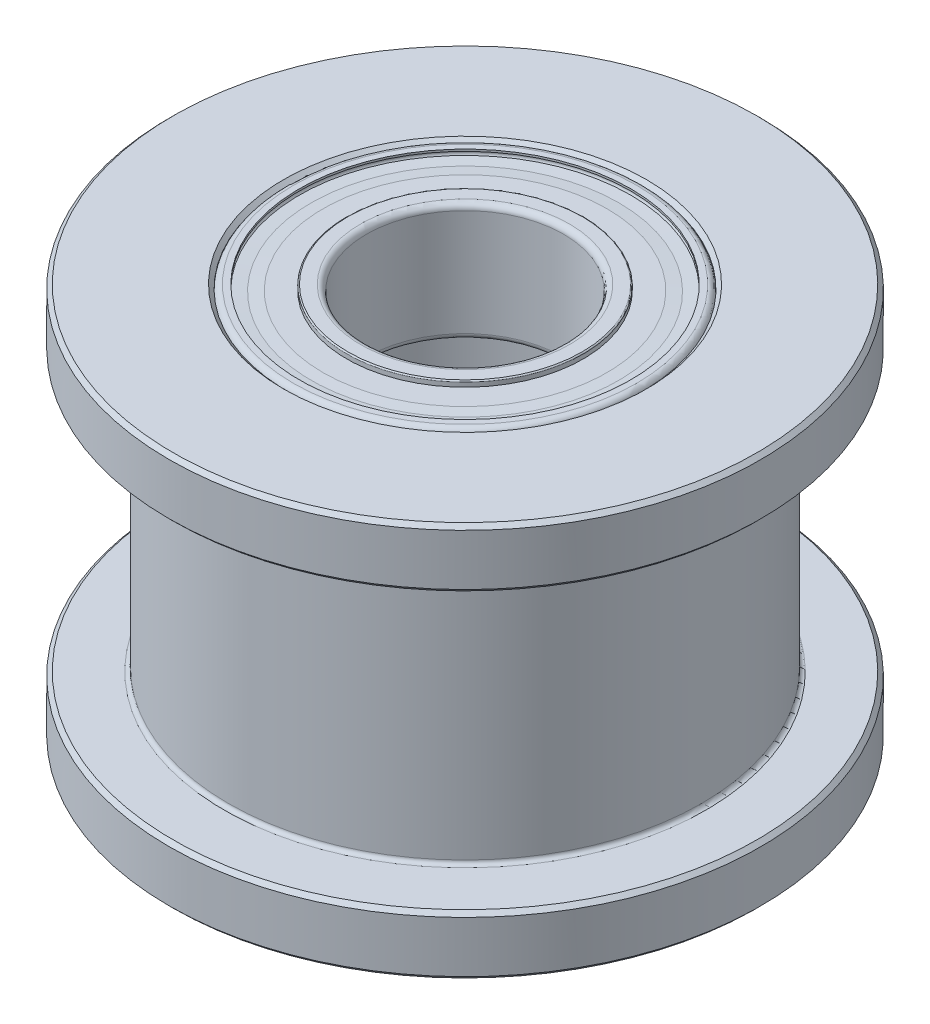
SolidWorks part; units mm, degrees
material "6061-T6 (SS)"
ref_plane "Přední rovina" through (0, 0, 0) normal (0, 0, 1) x (1, 0, 0)
ref_plane "Horní rovina" through (0, 0, 0) normal (0, 1, 0) x (1, 0, 0)
ref_plane "Pravá rovina" through (0, 0, 0) normal (1, 0, 0) x (0, 0, -1)
sketch "Skica1" plane through (0, 0, 0) normal (0, 0, 1) x (1, 0, 0)
  line L0 (4.5, 10) -> (7.5, 10)
  line L1 (7.5, 10) -> (7.5, 8.5)
  line L2 (7.5, 8.5) -> (6, 8.5)
  line L3 (6, 8.5) -> (6, 1.5)
  line L4 (6, 1.5) -> (7.5, 1.5)
  line L5 (7.5, 1.5) -> (7.5, 0)
  line L6 (7.5, 0) -> (4.5, 0)
  line L8 (4.5, 10) -> (4.5, 7)
  line L9 (4.5, 7) -> (3.5, 7)
  line L10 (3.5, 7) -> (3.5, 3)
  line L11 (3.5, 3) -> (4.5, 3)
  line L12 (4.5, 3) -> (4.5, 0)
  line L13 (0, 0) -> (0, -4.1646) construction
  dimension "D1" = 1.5
  dimension "D2" = 7
  dimension "D3" = 4.5
  dimension "D4" = 3.5
  dimension "D5" = 6
  dimension "D6" = 3
  dimension "D7" = 7.5
revolve "Rotovat1" add sketch "Skica1" angle 360 about L13
chamfer "Zkosení1" distance 0.1 angle 45 8 edges at (0, 3, 3.5) (0, 0, 4.5) (0, 7, 3.5) (0, 0, 7.5) (0, 1.5, 7.5) (0, 8.5, 7.5) (0, 10, 7.5) (0, 10, 4.5)
fillet "Zaoblit1" radius 0.1 4 edges at (0, 3, 4.5) (0, 1.5, 6) (0, 8.5, 6) (0, 7, 4.5)
sketch "Skica4" plane through (0, 0, 0) normal (0, 0, 1) x (1, 0, 0)
  line L0 (4.5, 9.85) -> (4.5, 7.15)
  line L1 (4.35, 7) -> (4.2, 7)
  line L2 (4.2, 7) -> (4.2, 7.05)
  line L3 (3.85, 7.2828) -> (4.2132, 7.229)
  line L4 (3.85, 7.2828) -> (3.85, 8.0528)
  line L5 (3.85, 8.9472) -> (3.85, 9.7172)
  line L6 (3.85, 9.7172) -> (4.2132, 9.771)
  line L7 (4.35, 10) -> (4.2, 10)
  line L8 (4.2, 10) -> (4.2, 9.95)
  line L9 (0, 0) -> (0, 18.4294) construction
  line L10 (4.4, 7) -> (-4.4, 7) construction
  arc A0 (4.35, 10) -> (4.5, 9.85) centre (4.35, 9.85) cw
  arc A1 (4.35, 7) -> (4.5, 7.15) centre (4.35, 7.15) ccw
  arc A2 (4.2, 9.95) -> (4.2132, 9.771) centre (4.2, 9.86) cw
  arc A3 (3.85, 8.9472) -> (3.85, 8.0528) centre (3.45, 8.5) cw
  arc A4 (4.2, 7.05) -> (4.2132, 7.229) centre (4.2, 7.14) ccw
  point P26 (4.5, 8.5)
  point P29 (4.275, 7)
  dimension "D3" = 0.09
  dimension "D6" = 0.15
  dimension "D7" = 0.6
  dimension "D1" = 4.5
  dimension "D2" = 3.85
  dimension "D4" = 0.05
  dimension "D5" = 0.15
  dimension "D8" = 0.77
  dimension "D9" = 3
  dimension "D10" = 1.05
revolve "Rotovat2" add sketch "Skica4" angle 360 about L9
sketch "Skica5" plane through (0, 0, 0) normal (0, 0, 1) x (1, 0, 0)
  line L0 (2.5, 9.85) -> (2.5, 7.15)
  line L1 (2.65, 10) -> (2.97, 10)
  line L2 (3, 9.97) -> (3, 9.86)
  line L3 (3, 9.86) -> (3.6, 9.86)
  line L4 (3.6, 9.86) -> (3.9, 9.84)
  line L5 (3.9, 9.84) -> (4.2, 9.86)
  line L6 (4.2, 9.86) -> (4.2, 9.81)
  line L7 (4.2, 9.81) -> (3.9, 9.77)
  line L8 (3.9, 9.77) -> (3.6, 9.77)
  line L9 (3.6, 9.77) -> (3, 9.81)
  line L10 (3, 9.81) -> (3, 8.8969)
  line L11 (2.65, 7) -> (2.97, 7)
  line L12 (0, 0) -> (0, 20.363) construction
  line L13 (3, 7.03) -> (3, 7.14)
  line L21 (3, 7.19) -> (3, 8.1031)
  line L22 (3, 7.14) -> (3.6, 7.14)
  line L23 (3.6, 7.14) -> (3.8962, 7.1917)
  line L24 (3.8962, 7.1917) -> (4.1924, 7.14)
  line L25 (4.1924, 7.14) -> (4.1924, 7.19)
  line L26 (4.1924, 7.19) -> (3.8975, 7.2581)
  line L27 (3.8975, 7.2581) -> (3.5975, 7.2581)
  line L28 (3.5975, 7.2581) -> (3, 7.19)
  line L29 (-4.2, 7) -> (4.2, 7) construction
  arc A0 (2.65, 7) -> (2.5, 7.15) centre (2.65, 7.15) cw
  arc A1 (2.65, 10) -> (2.5, 9.85) centre (2.65, 9.85) ccw
  arc A2 (3, 9.97) -> (2.97, 10) centre (2.97, 9.97) ccw
  arc A3 (3, 7.03) -> (2.97, 7) centre (2.97, 7.03) cw
  arc A4 (3, 8.8969) -> (3, 8.1031) centre (3.45, 8.5) ccw
  dimension "D3" = 0.15
  dimension "D4" = 0.11
  dimension "D5" = 0.03
  dimension "D7" = 0.6
  dimension "D1" = 2.5
  dimension "D2" = 3
  dimension "D6" = 0.6
  dimension "D8" = 0.95
  dimension "D9" = 3
  dimension "D10" = 1.2
  dimension "D11" = 0.3
  dimension "D12" = 0.05
  dimension "D13" = 0.9
  dimension "D14" = 0.6
  dimension "D15" = 0.09
  dimension "D16" = 0.05
  dimension "D17" = 0.05
revolve "Rotovat3" add sketch "Skica5" angle 360 about L12
sketch "Skica6" plane through (0, 0, 0) normal (0, 0, 1) x (1, 0, 0)
  line L0 (3.45, 9.1) -> (3.45, 7.9)
  line L4 (-4.2, 7) -> (4.2, 7) construction
  arc A0 (3.45, 9.1) -> (3.45, 7.9) centre (3.45, 8.5) cw
  dimension "D1" = 0.6
  dimension "D2" = 1.5
  dimension "D3" = 3.45
revolve "Rotovat4" add sketch "Skica6" angle 360 about L0
pattern_circular "Kruhové pole1" count 8 over 360 about axis through (0, 0, 0) along (0, 1, 0) of bodies 105
sketch "Skica7" plane through (0, 0, 0) normal (0, 0, 1) x (1, 0, 0)
  line L0 (4.5, 2.85) -> (4.5, 0.15)
  line L1 (4.35, 0) -> (4.2, 0)
  line L2 (4.2, 0) -> (4.2, 0.05)
  line L3 (3.85, 0.2828) -> (4.2132, 0.229)
  line L4 (3.85, 0.2828) -> (3.85, 1.0528)
  line L5 (3.85, 1.9472) -> (3.85, 2.7172)
  line L6 (3.85, 2.7172) -> (4.2132, 2.771)
  line L7 (4.35, 3) -> (4.2, 3)
  line L8 (4.2, 3) -> (4.2, 2.95)
  line L9 (0, 0) -> (0, 11.2374) construction
  arc A0 (4.35, 3) -> (4.5, 2.85) centre (4.35, 2.85) cw
  arc A1 (4.35, 0) -> (4.5, 0.15) centre (4.35, 0.15) ccw
  arc A2 (4.2, 2.95) -> (4.2132, 2.771) centre (4.2, 2.86) cw
  arc A3 (3.85, 1.9472) -> (3.85, 1.0528) centre (3.45, 1.5) cw
  arc A4 (4.2, 0.05) -> (4.2132, 0.229) centre (4.2, 0.14) ccw
  point P19 (4.5, 1.5)
  point P20 (4.275, 0)
  dimension "D1" = 0.09
  dimension "D4" = 0.15
  dimension "D5" = 0.6
  dimension "D2" = 0.05
  dimension "D3" = 0.15
  dimension "D6" = 0.77
  dimension "D7" = 3
  dimension "D8" = 1.05
  dimension "D9" = 4.5
  dimension "D10" = 3.85
revolve "Rotovat5" add sketch "Skica7" angle 360 about L9
sketch "Skica8" plane through (0, 0, 0) normal (0, 0, 1) x (1, 0, 0)
  line L0 (2.5, 2.85) -> (2.5, 0.15)
  line L1 (2.65, 3) -> (2.97, 3)
  line L2 (3, 2.97) -> (3, 2.86)
  line L3 (3, 2.86) -> (3.6, 2.86)
  line L4 (3.6, 2.86) -> (3.9, 2.84)
  line L5 (3.9, 2.84) -> (4.2, 2.86)
  line L6 (4.2, 2.86) -> (4.2, 2.81)
  line L7 (4.2, 2.81) -> (3.9, 2.77)
  line L8 (3.9, 2.77) -> (3.6, 2.77)
  line L9 (3.6, 2.77) -> (3, 2.81)
  line L10 (3, 2.81) -> (3, 1.8969)
  line L11 (2.65, 0) -> (2.97, 0)
  line L12 (3, 0.03) -> (3, 0.14)
  line L13 (3, 0.19) -> (3, 1.1031)
  line L14 (3, 0.14) -> (3.6, 0.14)
  line L15 (3.6, 0.14) -> (3.8962, 0.1917)
  line L16 (3.8962, 0.1917) -> (4.1924, 0.14)
  line L17 (4.1924, 0.14) -> (4.1924, 0.19)
  line L18 (4.1924, 0.19) -> (3.8975, 0.2581)
  line L19 (3.8975, 0.2581) -> (3.5975, 0.2581)
  line L20 (3.5975, 0.2581) -> (3, 0.19)
  line L21 (0, 0) -> (0, -2.9362) construction
  arc A0 (2.65, 0) -> (2.5, 0.15) centre (2.65, 0.15) cw
  arc A1 (2.65, 3) -> (2.5, 2.85) centre (2.65, 2.85) ccw
  arc A2 (3, 2.97) -> (2.97, 3) centre (2.97, 2.97) ccw
  arc A3 (3, 0.03) -> (2.97, 0) centre (2.97, 0.03) cw
  arc A4 (3, 1.8969) -> (3, 1.1031) centre (3.45, 1.5) ccw
  dimension "D1" = 0.15
  dimension "D2" = 0.03
  dimension "D5" = 0.6
  dimension "D3" = 0.11
  dimension "D4" = 0.6
  dimension "D6" = 0.95
  dimension "D7" = 3
  dimension "D8" = 1.2
  dimension "D9" = 0.3
  dimension "D10" = 0.05
  dimension "D11" = 0.9
  dimension "D12" = 0.6
  dimension "D13" = 0.09
  dimension "D14" = 0.05
  dimension "D15" = 0.05
  dimension "D16" = 2.5
  dimension "D17" = 3
revolve "Rotovat6" add sketch "Skica8" angle 360 about L21
sketch "Skica9" plane through (0, 0, 0) normal (0, 0, 1) x (1, 0, 0)
  line L0 (3.45, 2.1) -> (3.45, 0.9)
  line L1 (0, -2.351) -> (0, 5.6956) construction
  arc A0 (3.45, 2.1) -> (3.45, 0.9) centre (3.45, 1.5) cw
  dimension "D1" = 0.6
  dimension "D2" = 3.45
  dimension "D3" = 1.5
revolve "Rotovat7" add sketch "Skica9" angle 360 about L0
pattern_circular "Kruhové pole3" count 8 over 360 about axis through (0, 0, 0) along (0, 1, 0) reverse direction yes of bodies 123
